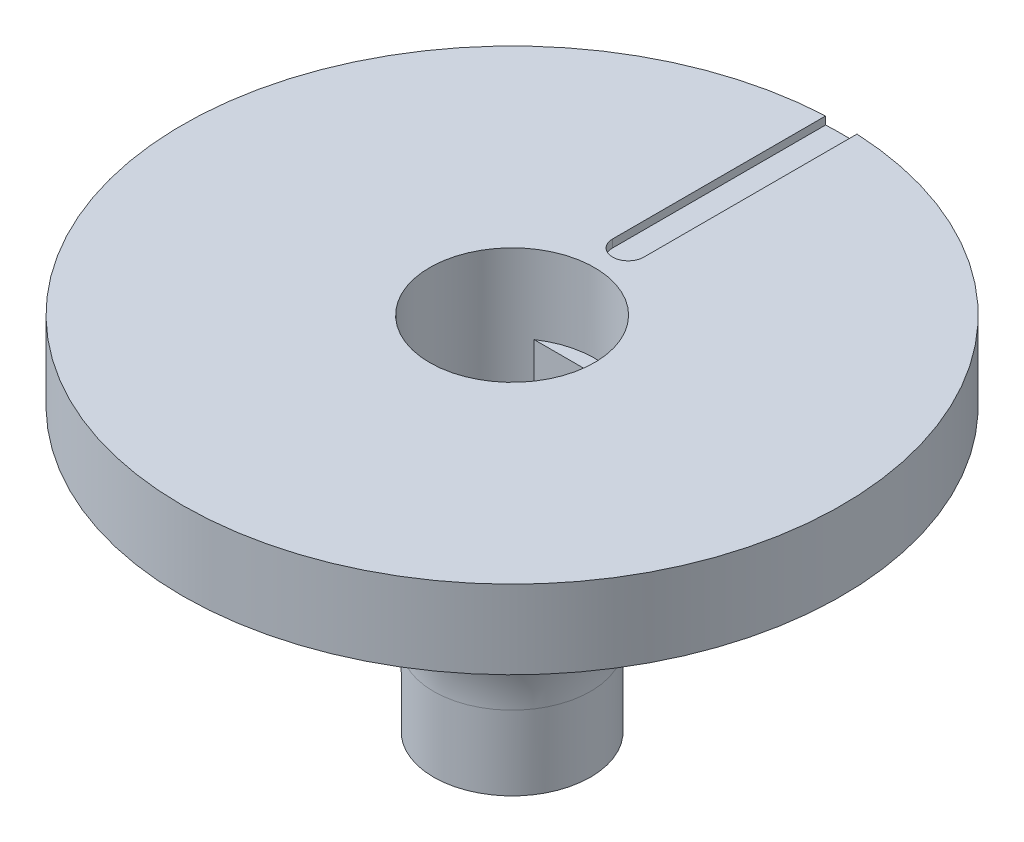
SolidWorks part; units mm, degrees
material "ABS"
ref_plane "Front Plane" through (0, 0, 0) normal (0, 0, 1) x (1, 0, 0)
ref_plane "Top Plane" through (0, 0, 0) normal (0, 1, 0) x (1, 0, 0)
ref_plane "Right Plane" through (0, 0, 0) normal (1, 0, 0) x (0, 0, -1)
sketch "Sketch1" plane through (0, 0, 0) normal (0, 1, 0) x (1, 0, 0)
  circle A0 centre (0, 0) radius 8.6
  circle A1 centre (0, 0) radius 10.5
  dimension "D1" = 17.2
  dimension "D2" = 21
extrude "Boss-Extrude1" add sketch "Sketch1" against normal blind 2
ref_plane "Plane1" through (0, 0, 8.6) normal (0, 0, -1) x (-1, 0, 0)
sketch "Sketch2" plane through (0, 0, 8.6) normal (0, 0, -1) x (-1, 0, 0)
  line L0 (0.4, -1.25) -> (-0.4, -1.25)
  line L1 (0.4, -1.25) -> (0.4, 0)
  line L6 (-0.4, 0) -> (-0.4, -1.25)
  line L7 (10.5, 0) -> (-10.5, 0) construction
  line L8 (0.4, 0) -> (-0.4, 0)
  point P2 (0, -1.25)
  dimension "D1" = 1.25
  dimension "D4" = 0.8
extrude "Boss-Extrude2" add sketch "Sketch2" along normal blind 1.25
ref_plane "Plane2" through (0, 0, -8.6) normal (0, 0, 1) x (1, 0, 0)
extrude "Boss-Extrude3" add sketch "Sketch2<2>" against normal blind 1.25 from surface starting at plane "Plane2"
sketch "Sketch2<2>" plane through (0, 0, 8.6) normal (0, 0, -1) x (-1, 0, 0) same geometry as "Sketch2"
sketch "Sketch3" plane through (0, 0, 0) normal (0, 1, 0) x (1, 0, 0)
  circle A1 centre (0, 0) radius 10.5
  circle A2 centre (0, 0) radius 10.5
  dimension "D1" = 0
extrude "Boss-Extrude4" add sketch "Sketch3" along normal blind 0.5
sketch "Sketch5" plane through (0, 0, 0) normal (0, -1, 0) x (1, 0, 0)
  circle A1 centre (0, 0) radius 3.25
  dimension "D2" = 6.5
extrude "Boss-Extrude5" add sketch "Sketch5" along normal blind 6
fillet "Fillet2" radius 0.75 1 edges at (0, 0, 3.25)
sketch "Sketch4" plane through (0, 0.5, 0) normal (0, 1, 0) x (1, 0, 0)
  line L0 (-1.4697, 2.175) -> (1.4697, 2.175)
  line L1 (-3.1755, -2.625) -> (3.3726, -2.625) construction
  arc A0 (-1.4697, 2.175) -> (1.4697, 2.175) centre (0, 0) ccw
  dimension "D1" = 5.25
  dimension "D2" = 4.8
extrude "Cut-Extrude1" cut sketch "Sketch4" against normal blind 5.5
fillet "Fillet1" radius 0.25 4 edges at (-0.4, -1.25, 7.9703) (0.4, -1.25, 7.9703) (-0.4, -1.25, -7.9703) (0.4, -1.25, -7.9703)
sketch "Sketch7" plane through (0, 0.5, 0) normal (0, 1, 0) x (1, 0, 0)
  circle A2 centre (0, 0) radius 2.625
  arc A3 (-1.4697, 2.175) -> (1.4697, 2.175) centre (0, 0) ccw construction
extrude "Cut-Extrude2" cut sketch "Sketch7" against normal blind 2.5
sketch "Sketch9" plane through (0, 0.5, 0) normal (0, 1, 0) x (1, 0, 0)
  line L0 (0, 3.7) -> (0, 13.7) construction
  line L1 (-0.5, 3.7) -> (-0.5, 13.7)
  line L2 (0.5, 3.7) -> (0.5, 13.7)
  arc A0 (-0.5, 3.7) -> (0.5, 3.7) centre (0, 3.7) ccw
  arc A1 (0.5, 13.7) -> (-0.5, 13.7) centre (0, 13.7) ccw
  point P3 (0, 8.7)
  dimension "D1" = 1
  dimension "D2" = 10
  dimension "D3" = 3.7
extrude "Cut-Extrude3" cut sketch "Sketch9" against normal blind 0.25
sketch "Sketch11" plane through (0, -6, 0) normal (0, -1, 0) x (1, 0, 0)
  circle A0 centre (0, 0) radius 2.5
  dimension "D1" = 5
extrude "Boss-Extrude6" add sketch "Sketch11" along normal blind 5
sketch "Sketch10" plane through (0, -6, 0) normal (0, -1, 0) x (1, 0, 0)
  line L1 (1.8042, 0) -> (0.9021, 1.5625)
  line L2 (0.9021, 1.5625) -> (-0.9021, 1.5625)
  line L3 (-0.9021, 1.5625) -> (-1.8042, 0)
  line L4 (-1.8042, 0) -> (-0.9021, -1.5625)
  line L5 (-0.9021, -1.5625) -> (0.9021, -1.5625)
  line L6 (0.9021, -1.5625) -> (1.8042, 0)
  circle A0 centre (0, 0) radius 1.5625 construction
  dimension "D1" = 3.125
extrude "Cut-Extrude4" cut sketch "Sketch10" against normal blind 4.5 from surface starting at face at (0, -11, -2.5)
chamfer "Chamfer2" distance 0.25 angle 45 6 edges at (-1.3532, -11, 0.7813) (-1.3532, -11, -0.7813) (0, -11, -1.5625) (1.3532, -11, -0.7813) (1.3532, -11, 0.7813) (0, -11, 1.5625)
fillet "Fillet3" radius 5 1 edges at (0, -6, -2.5)
ref_axis "Axis1" through (0, 1.075, 0) along (0, -1, 0)
